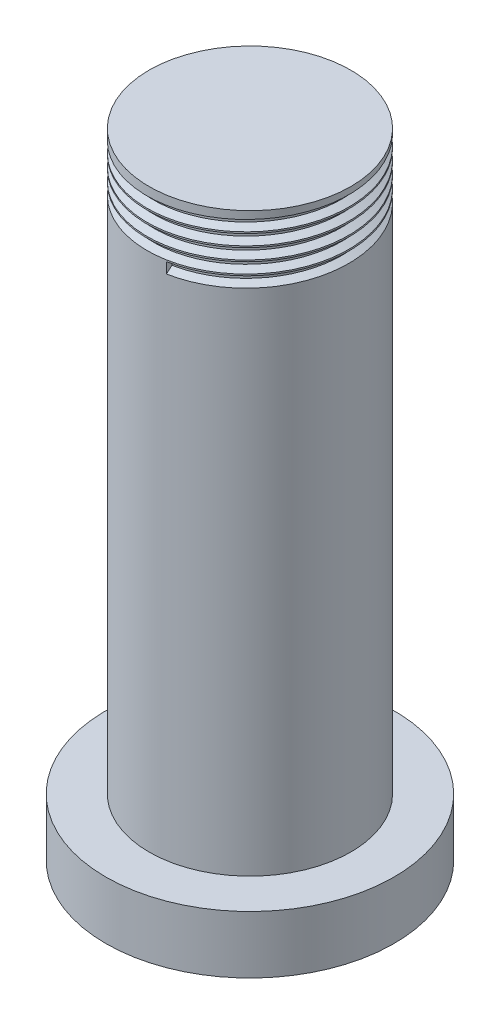
SolidWorks part; units mm, degrees
ref_plane "Alzado" through (0, 0, 0) normal (0, 0, 1) x (1, 0, 0)
ref_plane "Planta" through (0, 0, 0) normal (0, 1, 0) x (1, 0, 0)
ref_plane "Vista lateral" through (0, 0, 0) normal (1, 0, 0) x (0, 0, -1)
sketch "Croquis1" plane through (0, 0, 0) normal (0, 1, 0) x (1, 0, 0)
  circle A0 centre (0, 0) radius 25
  dimension "D1" = 50
extrude "Saliente-Extruir2" add sketch "Croquis1" along normal blind 10 contours A0
sketch "Croquis3" plane through (0, 10, 0) normal (0, 1, 0) x (1, 0, 0)
  circle A0 centre (0, 0) radius 17.5
  dimension "D1" = 35
extrude "Saliente-Extruir4" add sketch "Croquis3" along normal blind 90
sketch "Croquis4" plane through (0, 100, 0) normal (0, 1, 0) x (1, 0, 0)
  circle A0 centre (0, 0) radius 17.5
extrude "Saliente-Extruir6" add sketch "Croquis4" along normal blind 10
sketch "Croquis10" plane through (0, 110, 0) normal (0, 1, 0) x (1, 0, 0)
  circle A0 centre (0, 0) radius 17.5
curve "Hélice/Espiral2" pitch 2.5 height 10 turns 4
ref_plane "Plano3" through (-17.5, 110, 0) normal (0, -0.0227, -0.9997) x (-1, 0, 0)
thread "Rosca1" pitch 2.1167 method cut profile "Perfil de rosca1" start angle 0, offset 0, length 10, pitch 2.1167, diameter 35
ref_plane "Plano4" through (-17.5, 110, 0) normal (0, 0, 1) x (-1, 0, 0)
sketch "Perfil de rosca1" plane through (-17.5, 110, 0) normal (0, 0, 1) x (-1, 0, 0)
  line L0 (0, 0) -> (0, 2.1167) construction
  line L11 (0, 0) -> (0, 1.8521)
  line L12 (0, 1.8521) -> (-1.1457, 1.1906)
  line L13 (-1.1457, 1.1906) -> (-1.1457, 0.6615)
  line L15 (-1.1457, 0.6615) -> (0, 0)
  line L17 (-1.1457, 0.926) -> (0, 0.926) construction
  point P2 (0, 0)
  dimension "Pitch" = 2.1167
  dimension "Profile_Angle" = 60
  dimension "Profile_Land" = 0.5292
  dimension "Profile_Height" = 1.1457
